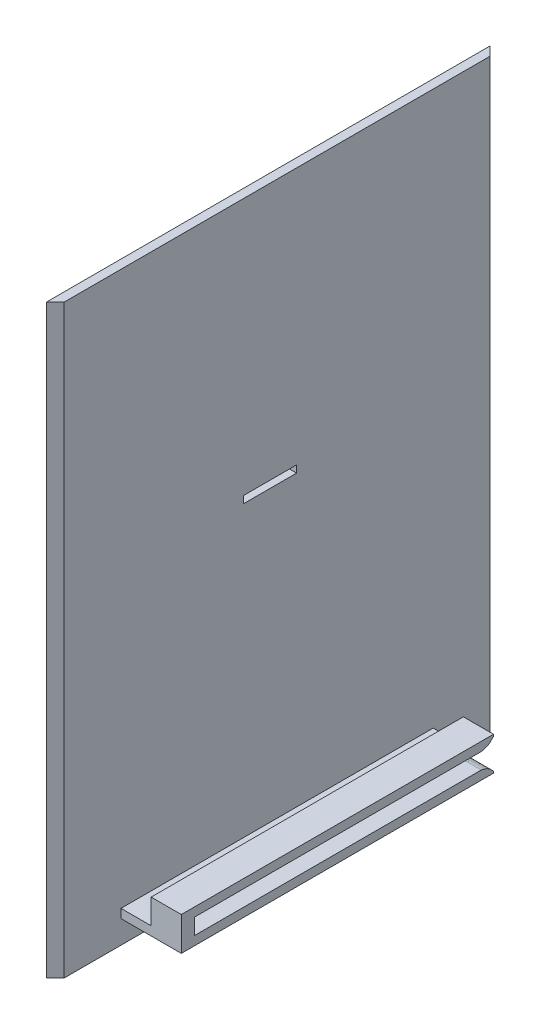
SolidWorks part; units mm, degrees
material "ABS"
ref_plane "Alzado" through (0, 0, 0) normal (0, 0, 1) x (1, 0, 0)
ref_plane "Planta" through (0, 0, 0) normal (0, 1, 0) x (1, 0, 0)
ref_plane "Vista lateral" through (0, 0, 0) normal (1, 0, 0) x (0, 0, -1)
sketch "Croquis1" plane through (0, 0, 0) normal (0, 1, 0) x (1, 0, 0)
  line L0 (0, 0) -> (0, 250)
  line L1 (0, 250) -> (-5, 250)
  line L2 (-5, 250) -> (-5, 0)
  line L3 (-5, 0) -> (0, 0)
  dimension "D1" = 250
  dimension "D2" = 250
  dimension "D3" = 5
extrude "Saliente-Extruir1" add sketch "Croquis1" along normal blind 330
sketch "Croquis2" plane through (0, 330, 0) normal (0, 1, 0) x (1, 0, 0)
  line L0 (0, 250) -> (0, 245)
  line L1 (0, 0) -> (0, 250) construction
  line L2 (0, 245) -> (-5, 250)
  line L3 (-5, 250) -> (0, 250)
  line L4 (-5, 0) -> (0, 5)
  line L5 (0, 5) -> (0, 0)
  line L6 (0, 0) -> (-5, 0)
  dimension "D1" = 5
  dimension "D2" = 5
extrude "Cortar-Extruir1" cut sketch "Croquis2" against normal up to next
sketch "Croquis3" plane through (0, 0, 0) normal (1, 0, 0) x (0, 0, -1)
  line L0 (37, 13) -> (213, 13)
  line L1 (213, 13) -> (213, 18)
  line L6 (213, 18) -> (37, 18)
  line L7 (37, 18) -> (37, 13)
  line L9 (5, 0) -> (245, 0) construction
  line L12 (5, 0) -> (5, 330) construction
  line L13 (245, 0) -> (245, 330) construction
  dimension "D1" = 5
  dimension "D2" = 18
  dimension "D3" = 32
  dimension "D4" = 32
extrude "Saliente-Extruir2" add sketch "Croquis3" along normal blind 34
sketch "Croquis4" plane through (0, 18, 0) normal (0, 1, 0) x (1, 0, 0)
  line L0 (34, 213) -> (0, 213) construction
  line L1 (22, 213) -> (17, 213)
  line L2 (22, 213) -> (22, 37)
  line L3 (22, 37) -> (17, 37)
  line L4 (17, 213) -> (17, 37)
  line L5 (34, 37) -> (0, 37) construction
  dimension "D1" = 12
  dimension "D2" = 5
extrude "Saliente-Extruir3" add sketch "Croquis4" along normal blind 9
sketch "Croquis5" plane through (0, 27, 0) normal (0, 1, 0) x (1, 0, 0)
  line L1 (17, 213) -> (34, 213)
  line L2 (17, 213) -> (17, 37)
  line L3 (17, 37) -> (34, 37)
  line L4 (34, 213) -> (34, 37)
extrude "Saliente-Extruir4" add sketch "Croquis5" along normal blind 5
fillet "Redondeo1" radius 4 3 edges at (28, 18, -213) (28, 27, -213) (22, 22.5, -213) profile chamfer
fillet "Redondeo2" radius 7 3 edges at (28, 27, -209) (22, 22.5, -209) (28, 18, -209) conic rho 0.3
sketch "Croquis6" plane through (0, 18, 0) normal (0, 1, 0) x (1, 0, 0)
  line L0 (22, 37) -> (22, 206.1005) construction
  line L1 (34, 37) -> (22, 37)
  line L2 (34, 37) -> (34, 44.3342)
  line L3 (34, 44.3342) -> (22, 44.3342)
  line L4 (22, 37) -> (22, 44.3342)
extrude "Saliente-Extruir5" add sketch "Croquis6" along normal blind 9
sketch "Croquis7" plane through (-5, 0, 0) normal (-1, 0, 0) x (0, 0, 1)
  line L0 (0, 330) -> (0, 0) construction
  line L1 (-136, 185) -> (-106, 185)
  line L2 (-136, 185) -> (-136, 181)
  line L3 (-136, 181) -> (-106, 181)
  line L4 (-106, 185) -> (-106, 181)
  line L5 (-250, 0) -> (0, 0) construction
  dimension "D1" = 30
  dimension "D2" = 4
  dimension "D3" = 106
  dimension "D4" = 181
extrude "Cortar-Extruir2" cut sketch "Croquis7" against normal up to next
